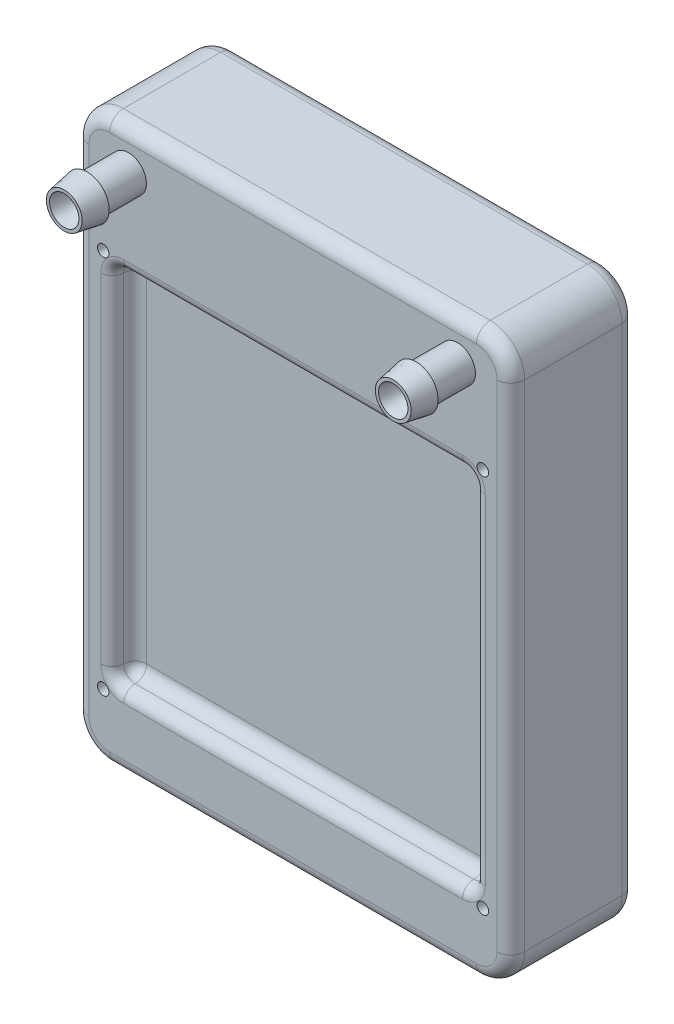
SolidWorks part; units mm, degrees
material "Rubber"
ref_plane "Front" through (0, 0, 0) normal (0, 0, 1) x (1, 0, 0)
ref_plane "Top" through (0, 0, 0) normal (0, 1, 0) x (1, 0, 0)
ref_plane "Right" through (0, 0, 0) normal (1, 0, 0) x (0, 0, -1)
sketch "Sketch1" plane through (0, 0, 0) normal (0, 0, 1) x (1, 0, 0)
  line L0 (52.5, 45) -> (52.5, -60) construction
  line L1 (-60.25, 78) -> (60.25, 78)
  line L2 (-60.25, 78) -> (-60.25, -78)
  line L3 (-60.25, -78) -> (60.25, -78)
  line L4 (60.25, 78) -> (60.25, -78)
  line L5 (-60.25, 78) -> (60.25, -78) construction
  line L6 (-60.25, -78) -> (60.25, 78) construction
  line L7 (52.5, -60) -> (-52.5, -60) construction
  line L9 (52.5, 45) -> (-52.5, 45) construction
  line L11 (-52.5, -60) -> (-52.5, 45) construction
  line L12 (-52.5, -7.5) -> (-60.25, -7.5) construction
  line L13 (52.5, -7.5) -> (60.25, -7.5) construction
  circle A0 centre (-52.5, 45) radius 1.5875
  circle A1 centre (52.5, 45) radius 1.5875
  circle A2 centre (52.5, -60) radius 1.5875
  circle A3 centre (-52.5, -60) radius 1.5875
  point P0 (0, 0)
  point P6 (0, 0)
  dimension "D3" = 3.175
  dimension "D1" = 156
  dimension "D2" = 120.5
  dimension "D4" = 105
  dimension "D5" = 105
  dimension "D6" = 18
extrude "Boss-Extrude1" add sketch "Sketch1" along normal mid plane 34.544
sketch "Sketch2" plane through (0, 0, 17.272) normal (0, 0, 1) x (1, 0, 0)
  line L0 (-45.5, 67) -> (45.5, 67) construction
  line L1 (0, 67) -> (0, 0) construction
  line L2 (60.25, 78) -> (-60.25, 78) construction
  circle A0 centre (-45.5, 67) radius 4.953
  circle A1 centre (45.5, 67) radius 4.953
  circle A2 centre (-45.5, 67) radius 4.064
  circle A3 centre (45.5, 67) radius 4.064
  dimension "D1" = 9.906
  dimension "D4" = 8.128
  dimension "D2" = 91
  dimension "D3" = 11
extrude "Boss-Extrude2" add sketch "Sketch2" along normal blind 17.78
sketch "Sketch3" plane through (0, 0, 35.052) normal (0, 0, 1) x (1, 0, 0)
  circle A0 centre (-45.5, 67) radius 4.064 construction
  circle A1 centre (-45.5, 67) radius 4.953
  circle A2 centre (-45.5, 67) radius 4.953
  circle A3 centre (45.5, 67) radius 4.953
  circle A4 centre (45.5, 67) radius 4.953
  circle A5 centre (-45.5, 67) radius 4.064
  circle A6 centre (45.5, 67) radius 4.064 construction
  circle A7 centre (45.5, 67) radius 4.064
  dimension "D1" = 0
  dimension "D2" = 0
extrude "Boss-Extrude3" add sketch "Sketch3" against normal blind 6.35 draft 10 draft outward yes
fillet "Fillet1" radius 3.81 8 edges at (0, -78, 17.272) (60.25, 0, 17.272) (0, 78, 17.272) (-60.25, 0, 17.272) (60.25, 0, -17.272) (0, -78, -17.272) (-60.25, 0, -17.272) (0, 78, -17.272)
fillet "Fillet2" radius 9.525 12 edges at (59.1341, 76.8841, -16.1561) (59.1341, 76.8841, 16.1561) (-59.1341, 76.8841, -16.1561) (-59.1341, 76.8841, 16.1561) (-59.1341, -76.8841, -16.1561) (-59.1341, -76.8841, 16.1561) (59.1341, -76.8841, -16.1561) (59.1341, -76.8841, 16.1561) (60.25, -78, 0) (-60.25, -78, 0) (-60.25, 78, 0) (60.25, 78, 0)
sketch "Sketch4" plane through (0, 0, 17.272) normal (0, 0, 1) x (1, 0, 0)
  line L0 (-52.5, 45) -> (52.5, -60) construction
  line L2 (-50, 42.5) -> (50, 42.5)
  line L3 (-50, 42.5) -> (-50, -57.5)
  line L4 (-50, -57.5) -> (50, -57.5)
  line L5 (50, 42.5) -> (50, -57.5)
  line L6 (-50, 42.5) -> (50, -57.5) construction
  line L7 (-50, -57.5) -> (50, 42.5) construction
  point P4 (0, -7.5)
  dimension "D1" = 100
extrude "Cut-Extrude1" cut sketch "Sketch4" against normal blind 6.35
fillet "Fillet3" radius 3.175 8 edges at (0, -57.5, 17.272) (50, -7.5, 17.272) (0, 42.5, 17.272) (-50, -7.5, 17.272) (0, -57.5, 10.922) (-50, -7.5, 10.922) (0, 42.5, 10.922) (50, -7.5, 10.922)
mirror "Mirror1" about plane through (0, 0, 0) normal (0, 0, 1) of "Fillet3", "Cut-Extrude1"
